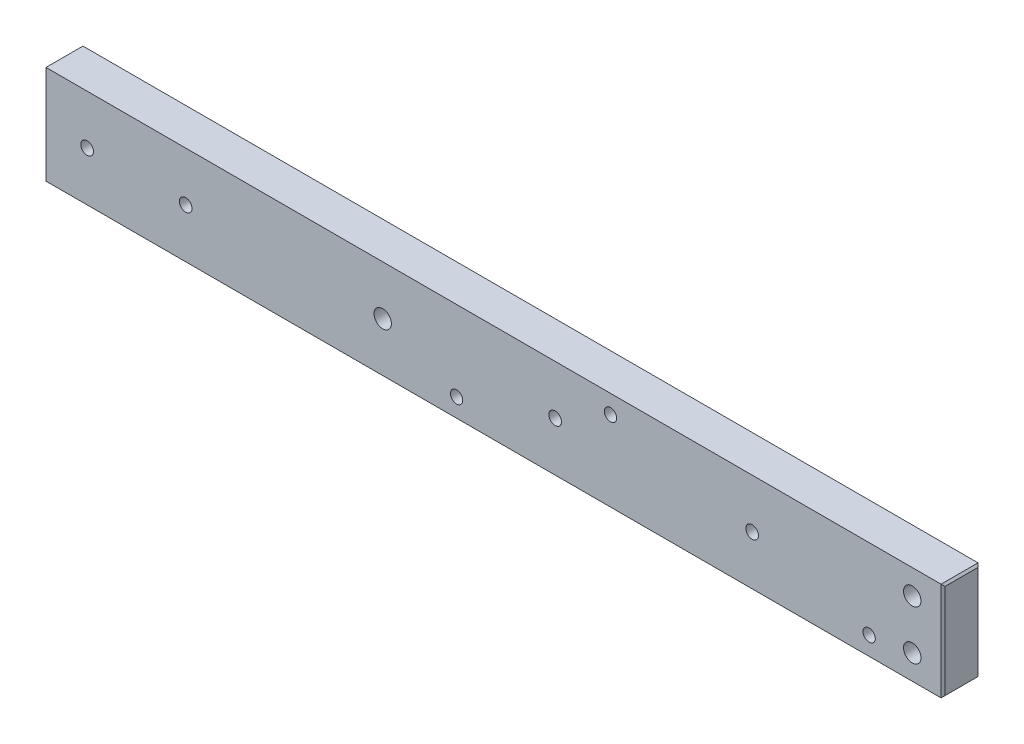
SolidWorks part; units mm, degrees
material "6061-T6 (SS)"
ref_plane "Front Plane" through (0, 0, 0) normal (0, 0, 1) x (1, 0, 0)
ref_plane "Top Plane" through (0, 0, 0) normal (0, 1, 0) x (1, 0, 0)
ref_plane "Right Plane" through (0, 0, 0) normal (1, 0, 0) x (0, 0, -1)
sketch "Sketch1" plane through (0, 0, 0) normal (0, 0, 1) x (1, 0, 0)
  line L1 (0, 0) -> (-231.775, 0)
  line L2 (0, 0) -> (0, 25.4)
  line L3 (0, 25.4) -> (-231.775, 25.4)
  line L4 (-231.775, 0) -> (-231.775, 25.4)
  dimension "D1" = 25.4
  dimension "D2" = 231.775
extrude "Boss-Extrude1" add sketch "Sketch1" along normal blind 9.525
sketch "Sketch2" plane through (0, 0, 9.525) normal (0, 0, 1) x (1, 0, 0)
  line L0 (-7.9375, 6.35) -> (-7.9375, 19.05)
  line L1 (-7.9375, 19.05) -> (-7.9375, 25.4)
  line L2 (0, 25.4) -> (-231.775, 25.4) construction
  line L3 (-7.9375, 6.35) -> (-7.9375, 0)
  line L4 (-231.775, 0) -> (0, 0) construction
  line L5 (0, 0) -> (0, 25.4) construction
  dimension "D1" = 7.9375
  dimension "D2" = 12.7
hole_wizard "#8 Clearance Hole1" positions "Sketch3" profile "Sketch4" hole size "#8" standard "ANSI Inch"
sketch "Sketch3" plane through (0, 0, 9.525) normal (0, 0, 1) x (1, 0, 0)
  point P0 (-7.9375, 6.35)
  point P3 (-7.9375, 19.05)
sketch "Sketch4" plane through (-7.9375, 6.35, 9.525) normal (1, 0, 0) x (0, -1, 0)
  line L0 (0, 0) -> (0, 26.7507)
  line L1 (0, 26.7507) -> (2.2479, 25.4)
  line L2 (2.2479, 25.4) -> (2.2479, 0)
  line L5 (2.2479, 0) -> (0, 0)
  line L10 (0, 26.7507) -> (-2.2479, 25.4) construction
  line L11 (0, -6.35) -> (0, 107.95) construction
  dimension "Hole Dia." = 4.4958
  dimension "Hole Depth" = 25.4
  dimension "Drill Angle" = 118
hole_wizard "#8 Clearance Hole2" positions "Sketch8" profile "Sketch9" hole size "#8" standard "ANSI Inch"
sketch "Sketch8" plane through (0, 0, 9.525) normal (0, 0, 1) x (1, 0, 0)
  line L0 (-207.9625, 12.7) -> (-144.4625, 12.7)
  line L1 (-207.9625, 12.7) -> (-231.775, 12.7)
  line L2 (-231.775, 25.4) -> (-231.775, 0) construction
  point P2 (-144.4625, 12.7)
  dimension "D1" = 63.5
  dimension "D2" = 23.8125
sketch "Sketch9" plane through (-144.4625, 12.7, 9.525) normal (1, 0, 0) x (0, -1, 0)
  line L0 (0, 0) -> (0, 20.4007)
  line L1 (0, 20.4007) -> (2.2479, 19.05)
  line L2 (2.2479, 19.05) -> (2.2479, 0)
  line L5 (2.2479, 0) -> (0, 0)
  line L10 (0, 20.4007) -> (-2.2479, 19.05) construction
  line L11 (0, -6.35) -> (0, 107.95) construction
  dimension "Hole Dia." = 4.4958
  dimension "Hole Depth" = 19.05
  dimension "Drill Angle" = 118
chamfer "Chamfer1" distance 0.508 angle 45 8 edges at (0, 0, 4.7625) (0, 12.7, 9.525) (0, 25.4, 4.7625) (0, 12.7, 0) (-231.775, 25.4, 4.7625) (-231.775, 12.7, 9.525) (-231.775, 0, 4.7625) (-231.775, 12.7, 0)
hole_wizard "#4 Clearance Hole1" positions "Sketch10" profile "Sketch12" hole size "#4" standard "ANSI Inch" end condition through all
sketch "Sketch10" plane through (0, 0, 0) normal (0, 0, -1) x (-1, 0, 0)
  point P0 (100.0125, 12.7)
  point P3 (49.2125, 12.7)
sketch "Sketch12" plane through (-100.0125, 12.7, 0) normal (1, 0, 0) x (0, 1, 0)
  line L0 (0, 0) -> (0, 9.525)
  line L1 (0, 9.525) -> (1.6319, 9.525)
  line L2 (1.6319, 9.525) -> (1.6319, 0)
  line L5 (1.6319, 0) -> (0, 0)
  line L11 (0, -6.35) -> (0, 107.95) construction
  dimension "Thru Hole Dia." = 3.2639
  dimension "Thru Hole Depth" = 9.525
hole_wizard "#4 Clearance Hole2" positions "Sketch13" profile "Sketch14" hole size "#4" standard "ANSI Inch" end condition up to next
sketch "Sketch13" plane through (0, 0, 9.525) normal (0, 0, 1) x (1, 0, 0)
  line L0 (-220.6625, 12.7) -> (-195.2625, 12.7)
  line L2 (-231.267, 25.4) -> (-231.267, 0) construction
  line L3 (-144.4625, 12.7) -> (-207.9625, 12.7) construction
  point P0 (-220.6625, 12.7)
  point P2 (-195.2625, 12.7)
  point P11 (-231.267, 12.7)
  dimension "D1" = 25.4
  dimension "D2" = 63.5
sketch "Sketch14" plane through (-220.6625, 12.7, 9.525) normal (1, 0, 0) x (0, -1, 0)
  line L0 (0, 0) -> (0, 9.525)
  line L1 (0, 9.525) -> (1.6319, 9.525)
  line L2 (1.6319, 9.525) -> (1.6319, 0)
  line L5 (1.6319, 0) -> (0, 0)
  line L11 (0, -6.35) -> (0, 107.95) construction
  dimension "Thru Hole Dia." = 3.2639
  dimension "Thru Hole Depth" = 9.525
hole_wizard "1/8 (0.125) Diameter Hole1" positions "Sketch15" profile "Sketch17" hole size "1/8" standard "ANSI Inch" end condition up to next
sketch "Sketch15" plane through (0, 0, 9.525) normal (0, 0, 1) x (1, 0, 0)
  line L1 (0, 24.892) -> (0, 0.508) construction
  line L2 (-85.725, 20.6375) -> (-19.05, 4.7625)
  line L6 (-231.267, 0) -> (-0.508, 0) construction
  line L7 (-231.267, 0) -> (-0.508, 0) construction
  line L8 (-0.508, 25.4) -> (-231.267, 25.4) construction
  line L9 (-131.7625, 0) -> (-131.7625, 25.4) construction
  point P0 (-19.05, 4.7625)
  point P2 (-85.725, 20.6375)
  point P22 (-125.4125, 4.7625)
  point P35 (0, 0)
  point P36 (-129.8787, 6.35)
  point P37 (-134.4483, 4.7625)
  point P38 (-124.7155, 4.7625)
  dimension "D1" = 85.725
  dimension "D2" = 19.05
  dimension "D3" = 4.7625
  dimension "D4" = 4.7625
  dimension "D5" = 6.35
  dimension "D6" = 4.7625
sketch "Sketch17" plane through (-19.05, 4.7625, 9.525) normal (1, 0, 0) x (0, -1, 0)
  line L0 (0, 0) -> (0, 9.525)
  line L1 (0, 9.525) -> (1.5875, 9.525)
  line L2 (1.5875, 9.525) -> (1.5875, 0)
  line L5 (1.5875, 0) -> (0, 0)
  line L11 (0, -6.35) -> (0, 107.95) construction
  dimension "Thru Hole Dia." = 3.175
  dimension "Thru Hole Depth" = 9.525
